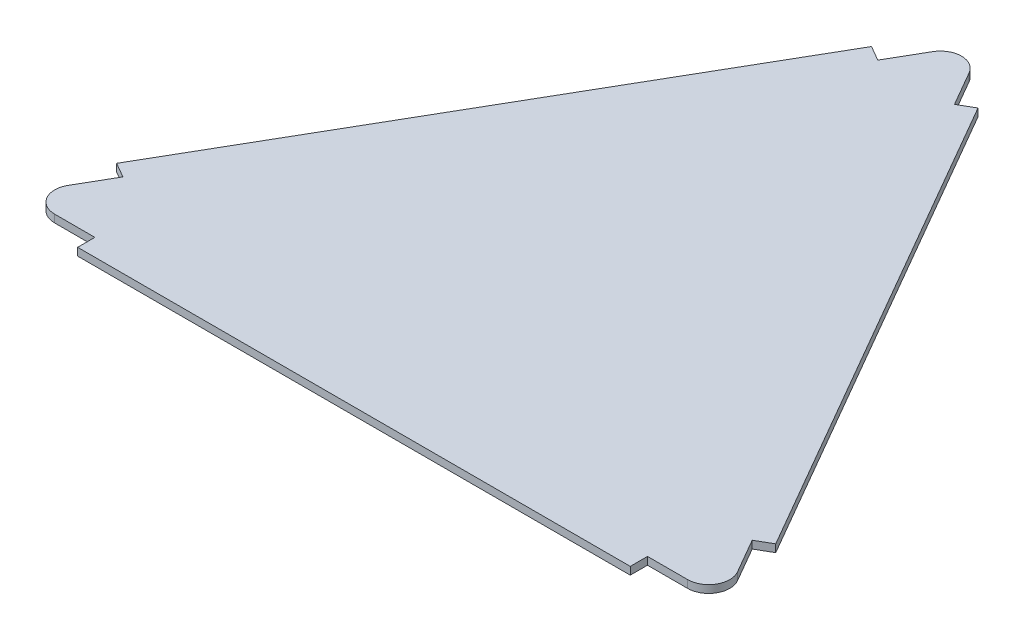
SolidWorks part; units mm, degrees
ref_plane "Front Plane" through (0, 0, 0) normal (0, 0, 1) x (1, 0, 0)
ref_plane "Top Plane" through (0, 0, 0) normal (0, 1, 0) x (1, 0, 0)
ref_plane "Right Plane" through (0, 0, 0) normal (1, 0, 0) x (0, 0, -1)
sketch "Sketch2" plane through (0, 0, 0) normal (0, 1, 0) x (1, 0, 0)
  line L0 (0, 0) -> (0, 115.4701) construction
  line L1 (-5.1962, 98.4701) -> (-87.8756, -44.735)
  line L2 (-8.6603, 100.4701) -> (-91.3397, -42.735)
  line L3 (-82.6795, -57.735) -> (82.6795, -57.735)
  line L4 (91.3397, -42.735) -> (8.6603, 100.4701)
  line L5 (-82.6795, -53.735) -> (82.6795, -53.735)
  line L6 (87.8756, -44.735) -> (5.1962, 98.4701)
  circle A0 centre (0, 0) radius 57.735 construction
  arc A1 (-91.3397, -42.735) -> (-82.6795, -57.735) centre (-82.6795, -47.735) ccw
  arc A2 (82.6795, -57.735) -> (91.3397, -42.735) centre (82.6795, -47.735) ccw
  arc A3 (8.6603, 100.4701) -> (-8.6603, 100.4701) centre (0, 95.4701) ccw
  arc A4 (-87.8756, -44.735) -> (-82.6795, -53.735) centre (-82.6795, -47.735) ccw
  arc A5 (82.6795, -53.735) -> (87.8756, -44.735) centre (82.6795, -47.735) ccw
  arc A6 (5.1962, 98.4701) -> (-5.1962, 98.4701) centre (0, 95.4701) ccw
  point P8 (-100, -57.735)
  point P11 (100, -57.735)
  dimension "D2" = 10
  dimension "D1" = 200
  dimension "D3" = 4
extrude "Boss-Extrude2" add sketch "Sketch2" along normal blind 2 contours L6 A6 L1 A4 L5 A5 | L4 A3 L2 A1 L3 A2 A6 L6 A5 L5 A4 L1 | L1 A4 L5 A5 L6 A6 | L2 A1 L3 A2 L4 A3 region at (0, 0, 0) region at (0, 0, -103.0004)
sketch "Sketch6" plane through (0, 2, 0) normal (0, 1, 0) x (1, 0, 0)
  line L2 (-8.6603, 100.4701) -> (-13.6603, 91.8098)
  line L3 (-8.6603, 100.4701) -> (-13.6603, 91.8098) construction
  line L6 (87.8756, -44.735) -> (5.1962, 98.4701)
  line L7 (-5.1962, 98.4701) -> (-87.8756, -44.735)
  line L8 (-82.6795, -53.735) -> (82.6795, -53.735)
  line L14 (-91.3397, -42.735) -> (-86.3397, -34.0748)
  line L21 (0, 101.4701) -> (0, 105.4701)
  line L22 (87.8756, -44.735) -> (5.1962, 98.4701) construction
  line L23 (91.3397, -42.735) -> (8.6603, 100.4701) construction
  line L32 (-10.0131, 89.1268) -> (-4.7631, 98.2201)
  line L33 (-13.9103, 91.3768) -> (-10.0131, 89.1268)
  line L35 (-5.1962, 98.4701) -> (-87.8756, -44.735) construction
  line L37 (-82.6795, -53.735) -> (82.6795, -53.735) construction
  line L40 (-82.6795, -57.735) -> (82.6795, -57.735) construction
  line L46 (-91.0897, -53.168) -> (-87.1729, -50.9067)
  line L47 (0, 101.4701) -> (0, 100.9701)
  line L48 (-13.6603, 91.8098) -> (-13.9103, 91.3768)
  line L49 (-14.3433, 91.6268) -> (-10.0131, 89.1268) construction
  line L50 (-86.3397, -34.0748) -> (-91.3397, -42.735) construction
  line L51 (-8.6603, 100.4701) -> (-91.3397, -42.735) construction
  line L53 (-10.1962, 89.8098) -> (-5.1962, 98.4701) construction
  line L54 (0.5, 100.9473) -> (0.5, 105.9581) construction
  line L55 (-9.0933, 100.7201) -> (-14.3433, 91.6268) construction
  line L56 (-13.6603, 91.8098) -> (-10.1962, 89.8098) construction
  line L57 (-86.0897, -33.6418) -> (-82.1926, -35.8918)
  line L58 (-82.1926, -35.8918) -> (-87.4426, -44.985)
  line L59 (-86.3397, -34.0748) -> (-86.0897, -33.6418)
  line L60 (-91.5124, -53.4121) -> (-87.1729, -50.9067) construction
  line L61 (-91.3397, -52.735) -> (-91.0897, -53.168)
  line L62 (-86.5228, -33.3918) -> (-82.1926, -35.8918) construction
  line L63 (-82.8756, -36.0748) -> (-87.8756, -44.735) construction
  line L64 (-86.3397, -34.0748) -> (-82.8756, -36.0748) construction
  line L65 (-91.7728, -42.485) -> (-86.5228, -33.3918) construction
  line L67 (-91.3397, -52.735) -> (-87.8756, -50.735) construction
  arc A0 (0, 105.4701) -> (-8.6603, 100.4701) centre (0, 95.4701) ccw
  arc A2 (8.6603, 100.4701) -> (-8.6603, 100.4701) centre (0, 95.4701) ccw construction
  arc A3 (-91.3397, -42.735) -> (-91.3397, -52.735) centre (-82.6795, -47.735) ccw construction
  arc A4 (82.6795, -57.735) -> (91.3397, -42.735) centre (82.6795, -47.735) ccw construction
  arc A5 (0, 105.4701) -> (-8.6603, 100.4701) centre (0, 95.4701) ccw construction
  arc A6 (5.1962, 98.4701) -> (-5.1962, 98.4701) centre (0, 95.4701) ccw
  arc A7 (-87.8756, -44.735) -> (-82.6795, -53.735) centre (-82.6795, -47.735) ccw
  arc A8 (82.6795, -53.735) -> (87.8756, -44.735) centre (82.6795, -47.735) ccw
  arc A11 (82.6795, -53.735) -> (87.8756, -44.735) centre (82.6795, -47.735) ccw construction
  arc A12 (5.1962, 98.4701) -> (-5.1962, 98.4701) centre (0, 95.4701) ccw construction
  arc A17 (0, 100.9701) -> (-4.7631, 98.2201) centre (0, 95.4701) ccw
  arc A18 (-91.3397, -42.735) -> (-91.3397, -52.735) centre (-82.6795, -47.735) ccw
  arc A20 (-91.3397, -42.735) -> (-82.6795, -57.735) centre (-82.6795, -47.735) ccw construction
  arc A21 (-87.8756, -44.735) -> (-82.6795, -53.735) centre (-82.6795, -47.735) ccw construction
  arc A25 (0.5, 100.9473) -> (-4.7631, 98.2201) centre (0, 95.4701) ccw construction
  arc A26 (-87.4426, -44.985) -> (-87.1729, -50.9067) centre (-82.6795, -47.735) ccw
  arc A27 (0, 101.4701) -> (-5.1962, 98.4701) centre (0, 95.4701) ccw construction
  arc A28 (0.5, 105.9581) -> (-9.0933, 100.7201) centre (0, 95.4701) ccw construction
  arc A31 (-87.8756, -44.735) -> (-87.8756, -50.735) centre (-82.6795, -47.735) ccw construction
  arc A32 (-91.7728, -42.485) -> (-91.5124, -53.4121) centre (-82.6795, -47.735) ccw construction
  point P20 (-46.5359, 26.8675)
  dimension "D3" = 0.5
  dimension "D1" = 4
  dimension "D2" = 0.5
ref_axis "Axis2" through (0, 0, 0) along (0, 1, 0)
extrude "Cut-Extrude1" cut sketch "Sketch6" against normal blind 5
pattern_circular "CirPattern1" count 3 over 360 about axis through (0, 0, 0) along (0, 1, 0) of "Cut-Extrude1"
